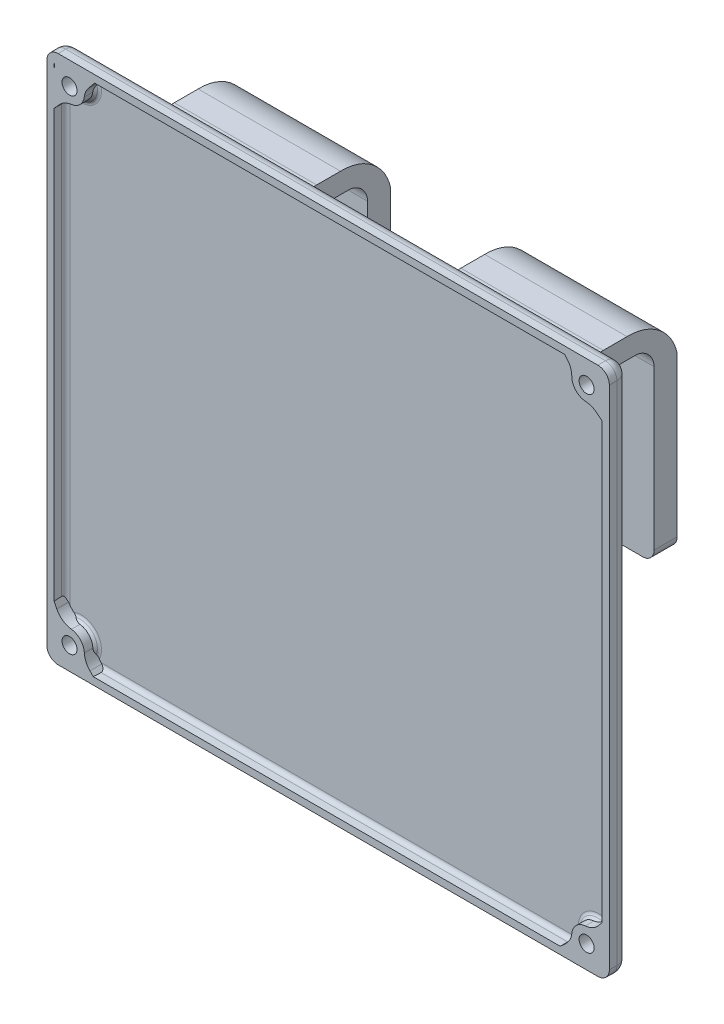
SolidWorks part; units mm, degrees
ref_plane "Front Plane" through (0, 0, 0) normal (0, 0, 1) x (1, 0, 0)
ref_plane "Top Plane" through (0, 0, 0) normal (0, 1, 0) x (1, 0, 0)
ref_plane "Right Plane" through (0, 0, 0) normal (1, 0, 0) x (0, 0, -1)
ref_plane "Plane1" through (0, 0, 429.1649) normal (0, 0, -1) x (-1, 0, 0)
sketch "Sketch1" plane through (0, 0, 429.1649) normal (0, 0, -1) x (-1, 0, 0)
  line L0 (65.6806, 95.3622) -> (65.681, -36.8209) construction
  line L1 (62.6815, -39.8205) -> (-78.0916, -39.821) construction
  line L4 (65.6806, 97.9127) -> (65.681, -39.8205)
  line L5 (65.681, -39.8205) -> (-80.6724, -39.821)
  line L6 (-80.6724, -39.821) -> (-80.6729, 97.9122)
  line L7 (-80.6729, 97.9122) -> (65.6806, 97.9127)
extrude "Boss-Extrude1- main body" add sketch "Sketch1" along normal blind 5
sketch "Sketch30" plane through (0, 0, 424.1649) normal (0, 0, -1) x (-1, 0, 0)
  line L0 (-80.6729, 97.9122) -> (-80.6724, -39.821) construction
  line L1 (-80.6724, -39.821) -> (65.681, -39.8205) construction
  line L2 (65.6806, 97.9127) -> (-80.6729, 97.9122) construction
  line L3 (65.681, -39.8205) -> (65.6806, 97.9127) construction
  point P0 (-74.6724, -33.821)
  point P1 (-74.6729, 91.9122)
  point P2 (59.6806, 91.9127)
  point P3 (59.681, -33.8205)
  point P12 (52.9714, 103.4147)
  dimension "D1" = 6
  dimension "D2" = 6
  dimension "D3" = 6
  dimension "D4" = 6
  dimension "D5" = 6
  dimension "D6" = 6
  dimension "D7" = 6
  dimension "D8" = 6
hole_wizard "CSK for M3.5 Cross Countersunk Head Screw2" positions "Sketch31" profile "Sketch32" countersink size "M3.5" standard "AS"
sketch "Sketch31" plane through (0, 0, 424.1649) normal (0, 0, -1) x (-1, 0, 0)
  point P0 (-74.6724, -33.821)
  point P3 (59.681, -33.8205)
  point P6 (59.6806, 91.9127)
  point P9 (-74.6729, 91.9122)
sketch "Sketch32" plane through (74.6724, -33.821, 424.1649) normal (1, 0, 0) x (0, 1, 0)
  line L0 (0, 0) -> (0, 9.9717)
  line L1 (0, 9.9717) -> (1.95, 8.8)
  line L2 (1.95, 8.8) -> (1.95, 1.9797)
  line L3 (1.95, 1.9797) -> (4, 0)
  line L5 (4, 0) -> (0, 0)
  line L6 (-1.95, 1.9797) -> (-4, 0) construction
  line L10 (0, 9.9717) -> (-1.95, 8.8) construction
  line L11 (0, -6.35) -> (0, 107.95) construction
  dimension "Hole Dia." = 3.9
  dimension "Hole Depth" = 8.8
  dimension "Near C'Sink Dia." = 8
  dimension "Near C'Sink Angle" = 92
  dimension "Drill Angle" = 118
draft "Draft2- 1degree" type of draft neutral plane draft angle 1 faces to draft 4 face at (-65.6808, 29.0461, 426.6649) face at (7.4962, 97.9125, 426.6649) face at (80.6727, 29.0456, 426.6649) face at (7.4957, -39.8207, 426.6649) neutral plane through (0, 0, 424.1649) neutral plane normal (0, 0, -1) reverse direction yes parameters "D1"=1
fillet "Fillet1- main body fillet" radius 3 12 edges at (80.6727, 29.0456, 424.1649) (7.4962, 97.9125, 424.1649) (-65.6808, 29.0461, 424.1649) (7.4957, -39.8207, 424.1649) (-65.6374, -39.7769, 426.6649) (80.6293, 97.8686, 426.6649) (80.6288, -39.7774, 426.6649) (-65.6369, 97.8691, 426.6649) (70.6729, 91.9122, 424.1649) (-63.6806, 91.9127, 424.1649) (-63.681, -33.8205, 424.1649) (70.6724, -33.821, 424.1649)
shell "Shell1- main body shell" thickness 1.9
sketch "Sketch33" plane through (0, 0, 429.1649) normal (0, 0, 1) x (1, 0, 0)
  line L0 (68.2722, 96.6762) -> (72.0252, 92.6043)
  line L1 (72.0252, 92.6043) -> (75.6004, 94.8362)
  line L2 (75.6004, 94.8362) -> (77.8295, 92.4177)
  line L3 (77.8295, 92.4177) -> (76.0958, 89.4661)
  line L4 (76.0958, 89.4661) -> (74.8608, 88.893)
  line L5 (74.8608, 88.893) -> (79.6666, 85.0847)
  line L6 (79.6666, 85.0847) -> (78.7944, 95.7659)
  line L7 (78.7944, 95.7659) -> (77.687, 96.2254)
  line L8 (77.687, 96.2254) -> (68.2722, 96.6762)
  line L9 (71.7871, -34.1665) -> (67.2146, -38.3807)
  line L10 (67.2146, -38.3807) -> (78.7992, -38.3807)
  line L11 (78.7992, -38.3807) -> (79.2842, -37.2118)
  line L12 (79.2842, -37.2118) -> (79.0417, -26.6251)
  line L13 (79.0417, -26.6251) -> (75.4783, -31.1218)
  line L14 (75.4783, -31.1218) -> (77.5847, -33.9805)
  line L15 (77.5847, -33.9805) -> (75.7676, -36.2736)
  line L16 (75.7676, -36.2736) -> (72.6792, -36.1257)
  line L17 (72.6792, -36.1257) -> (71.7871, -34.1665)
  line L18 (-56.8471, -34.4779) -> (-52.5324, -38.7926)
  line L19 (-52.5324, -38.7926) -> (-63.531, -38.1057)
  line L20 (-63.531, -38.1057) -> (-64.1538, -35.7926)
  line L21 (-64.1538, -35.7926) -> (-64.1538, -25.0342)
  line L22 (-64.1538, -25.0342) -> (-60.9738, -31.2809)
  line L23 (-60.9738, -31.2809) -> (-62.4655, -33.8205)
  line L24 (-62.4655, -33.8205) -> (-60.2891, -36.1818)
  line L25 (-60.2891, -36.1818) -> (-58.8735, -36.1818)
  line L26 (-58.8735, -36.1818) -> (-56.8471, -34.4779)
  line L27 (-64.4354, 84.185) -> (-60.2891, 88.6791)
  line L28 (-60.2891, 88.6791) -> (-61.743, 90.0205)
  line L29 (-61.743, 90.0205) -> (-62.2141, 93.1165)
  line L30 (-62.2141, 93.1165) -> (-59.9919, 94.8362)
  line L31 (-59.9919, 94.8362) -> (-56.6678, 92.6043)
  line L32 (-56.6678, 92.6043) -> (-56.5163, 91.8335)
  line L33 (-56.5163, 91.8335) -> (-52.5324, 96.6762)
  line L34 (-52.5324, 96.6762) -> (-62.9795, 96.4011)
  line L35 (-62.9795, 96.4011) -> (-63.531, 95.7307)
  line L36 (-63.531, 95.7307) -> (-64.4354, 84.185)
extrude "Boss-Extrude4" add sketch "Sketch33" against normal blind 3.6
fillet "Fillet5" radius 5 8 edges at (-56.0974, -35.2276, 428.058) (-61.4276, -30.3895, 428.058) (76.155, -30.2679, 428.058) (70.9798, -34.9105, 428.058) (71.1768, 93.5248, 428.058) (75.7244, 88.2086, 428.058) (-60.7247, 88.207, 428.058) (-55.8912, 92.5933, 428.058)
sketch "Sketch6" plane through (0, 0, 424.1649) normal (0, 0, -1) x (-1, 0, 0)
  line L0 (55.3818, 94.8599) -> (-70.3741, 94.8594) construction
  line L1 (-77.62, 87.6134) -> (-77.6196, -29.5222) construction
  line L7 (-63.2236, 75.7889) -> (-26.2236, 75.789)
  line L8 (-63.2236, 75.7889) -> (-63.2234, 31.5221)
  line L9 (-63.2234, 31.5221) -> (-26.2234, 31.5223)
  line L10 (-26.2236, 75.789) -> (-26.2234, 31.5223)
  line L11 (-63.2236, 75.7889) -> (-26.2234, 31.5223) construction
  line L12 (-63.2234, 31.5221) -> (-26.2236, 75.789) construction
  dimension "D1" = 19.0706
  dimension "D2" = 14.3964
  dimension "D3" = 44.2667
  dimension "D4" = 44.2667
  dimension "D5" = 37
extrude "Boss-Extrude6" add sketch "Sketch6" along normal blind 4
sketch "Sketch36" plane through (63.2233, -0.0002, 0) normal (1, 0, 0) x (0, 0, -1)
  line L0 (-420.1649, 75.7891) -> (-388.1583, 75.7891) construction
  line L1 (-420.1649, 31.5223) -> (-388.1583, 31.5223) construction
  line L2 (-400.1649, 75.7891) -> (-400.1649, 31.5223)
  line L3 (-420.1649, 75.7891) -> (-420.1649, 31.5223) construction
  line L4 (-415.0949, 80.7891) -> (-404.6564, 80.7891)
  line L5 (-400.1649, 31.5223) -> (-394.1649, 31.5223)
  line L6 (-394.1649, 31.5223) -> (-394.1649, 75.7891)
  line L7 (-413.3902, 86.0753) -> (-407.1941, 86.0753)
  line L8 (-424.1649, 75.7891) -> (-424.1649, 82.7982)
  line L9 (-424.1649, 87.6137) -> (-424.1649, -29.5219) construction
  line L12 (-424.1649, 75.7891) -> (-424.1649, 31.5223)
  line L13 (-424.1649, 31.5223) -> (-420.1649, 31.5223)
  line L14 (-420.1649, 31.5223) -> (-420.1649, 75.7891)
  line L15 (-420.1649, 75.7891) -> (-424.1649, 75.7891)
  line L16 (-424.1649, 75.7891) -> (-424.1649, 31.5223)
  line L17 (-424.1649, 31.5223) -> (-420.1649, 31.5223)
  line L18 (-420.1649, 31.5223) -> (-420.1649, 75.7891)
  arc A0 (-404.6564, 80.7891) -> (-400.1649, 75.7891) centre (-405.4592, 75.5506) cw
  arc A1 (-420.1649, 75.7891) -> (-415.0949, 80.7891) centre (-413.8114, 74.4171) cw
  arc A2 (-407.1941, 86.0753) -> (-394.1649, 75.7891) centre (-406.8793, 73.0791) cw
  arc A3 (-421.6288, 82.41) -> (-413.3902, 86.0753) centre (-413.6401, 75.545) cw
  arc A4 (-421.6288, 82.41) -> (-424.1649, 82.7982) centre (-422.7548, 83.5327) cw
  point P27 (-421.6233, 82.4092)
  point P31 (-424.1166, 82.6046)
  dimension "D4" = 13
  dimension "D5" = 0
  dimension "D6" = 1.59
  dimension "D7" = 5.2997
  dimension "D8" = 6.5
  dimension "D10" = 10.5333
  dimension "D11" = 10.3535
  dimension "D12" = 18.7057
  dimension "D13" = 17.2856
  dimension "D14" = 10.5249
  dimension "D16" = 1.4102
  dimension "D17" = 2.5426
  dimension "D1" = 20
  dimension "D2" = 5
  dimension "D3" = 6
  dimension "D9" = 6.1961
  dimension "D15" = 5.2862
extrude "Boss-Extrude7" add sketch "Sketch36" against normal up to surface (37 mm away) up to face at (26.2235, 53.6556, 422.1649)
ref_plane "Plane2" through (7.4958, 0, 0) normal (1, 0, 0) x (0, 0, -1)
sketch "Sketch37" plane through (0, 0, 394.1649) normal (0, 0, -1) x (-1, 0, 0)
  line L0 (-63.2236, 75.7889) -> (-26.2234, 31.5223) construction
  line L1 (-26.2236, 75.789) -> (-63.2234, 31.5221) construction
  line L3 (-51.2235, 60.1556) -> (-38.2235, 60.1556)
  line L4 (-51.2235, 60.1556) -> (-51.2235, 47.1556)
  line L5 (-51.2235, 47.1556) -> (-38.2235, 47.1556)
  line L6 (-38.2235, 60.1556) -> (-38.2235, 47.1556)
  line L7 (-51.2235, 60.1556) -> (-38.2235, 47.1556) construction
  line L8 (-51.2235, 47.1556) -> (-38.2235, 60.1556) construction
  point P8 (-44.7235, 53.6556)
  dimension "D1" = 13
  dimension "D2" = 13
extrude "Cut-Extrude1" cut sketch "Sketch37" against normal blind 16
fillet "Fillet6" radius 3 5 edges at (63.2234, 31.5221, 397.1649) (26.2234, 31.5223, 397.1649) (26.2235, 57.1602, 424.1649) (63.2235, 57.16, 424.1649) (44.7234, 31.5222, 424.1649)
mirror "Mirror1" about plane through (7.4958, 0, 0) normal (1, 0, 0) of "Fillet6", "Boss-Extrude6", "Boss-Extrude7", "Cut-Extrude1"
